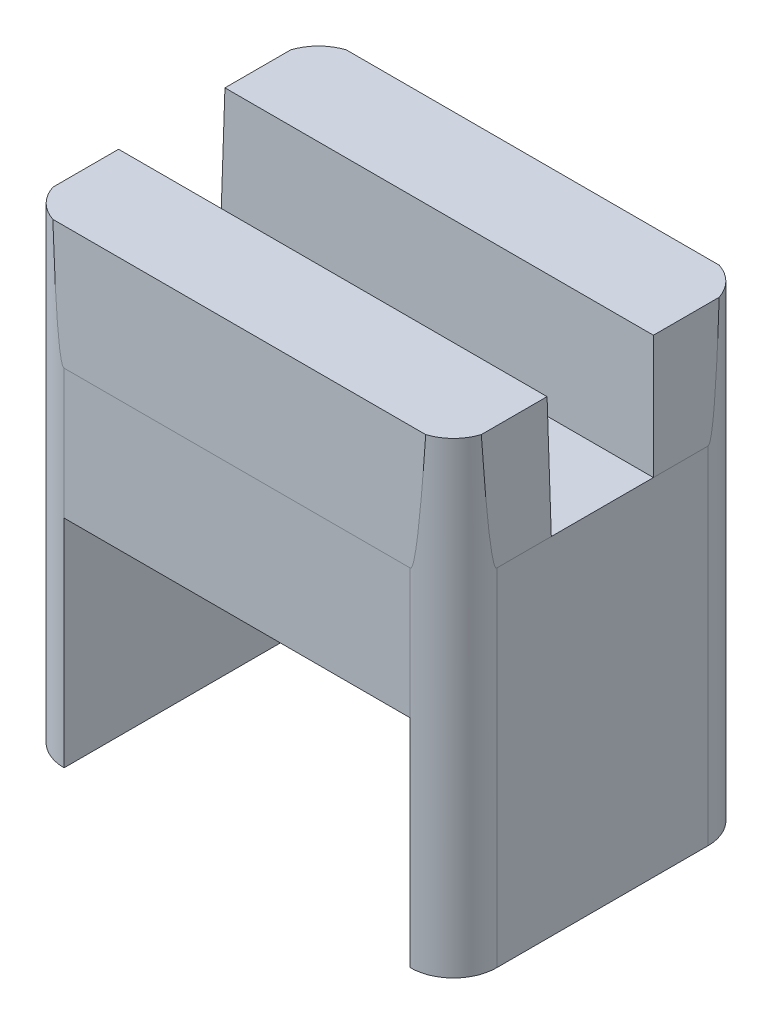
SolidWorks part; units mm, degrees
ref_plane "Front Plane" through (0, 0, 0) normal (0, 0, 1) x (1, 0, 0)
ref_plane "Top Plane" through (0, 0, 0) normal (0, 1, 0) x (1, 0, 0)
ref_plane "Right Plane" through (0, 0, 0) normal (1, 0, 0) x (0, 0, -1)
sketch "Sketch1" plane through (0, 0, 0) normal (0, 0, 1) x (1, 0, 0)
  line L0 (45, 0) -> (50, 0)
  line L1 (0, 0) -> (5, 0)
  line L2 (0, 0) -> (0, 40)
  line L3 (0, 40) -> (50, 40)
  line L4 (50, 0) -> (50, 40)
  line L6 (5, 0) -> (5, 25)
  line L7 (5, 25) -> (45, 25)
  line L8 (45, 0) -> (45, 25)
  point P9 (25, 40)
  point P10 (25, 25)
  dimension "D1" = 40
  dimension "D2" = 50
  dimension "D3" = 40
  dimension "D4" = 25
extrude "Boss-Extrude1" add sketch "Sketch1" along normal blind 34.4
sketch "Sketch2" plane through (0, 40, 0) normal (0, 1, 0) x (1, 0, 0)
  line L0 (50, -34.4) -> (50, 0) construction
  line L1 (0, 0) -> (50, 0)
  line L2 (0, 0) -> (0, -11.3)
  line L3 (0, -11.3) -> (50, -11.3)
  line L4 (50, 0) -> (50, -11.3)
  line L6 (0, -34.4) -> (50, -34.4)
  line L7 (0, -34.4) -> (0, -23.1)
  line L8 (0, -23.1) -> (50, -23.1)
  line L9 (50, -34.4) -> (50, -23.1)
  dimension "D1" = 11.8
extrude "Boss-Extrude2" add sketch "Sketch2" along normal blind 14 draft 1
fillet "Fillet1" radius 5 4 edges at (50, 20, 34.4) (50, 20, 0) (0, 20, 0) (0, 20, 34.4)
